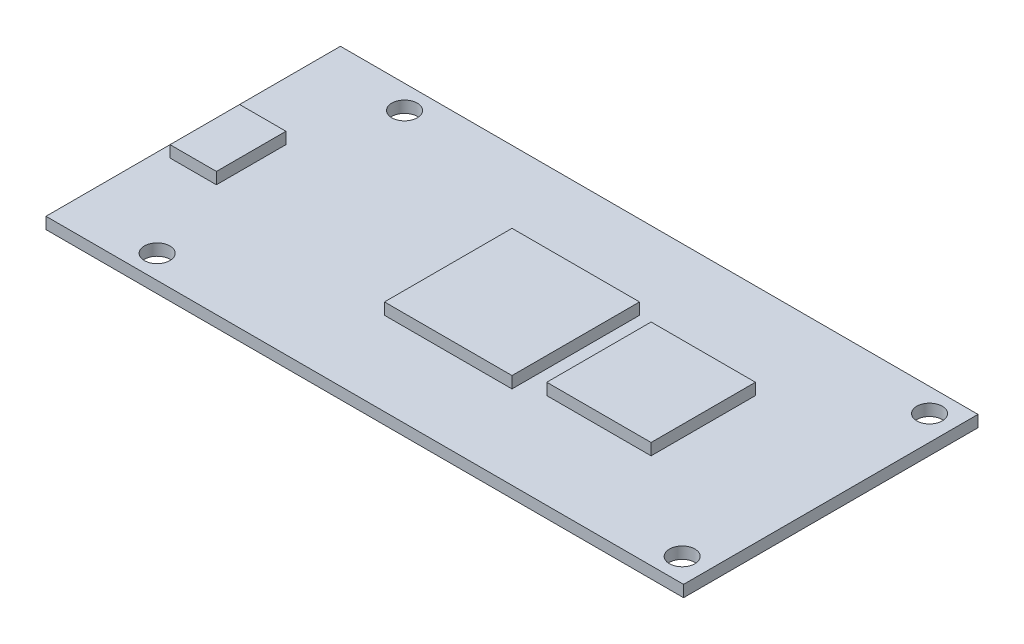
SolidWorks part; units mm, degrees
ref_plane "前视基准面" through (0, 0, 0) normal (0, 0, 1) x (1, 0, 0)
ref_plane "上视基准面" through (0, 0, 0) normal (0, 1, 0) x (1, 0, 0)
ref_plane "右视基准面" through (0, 0, 0) normal (1, 0, 0) x (0, 0, -1)
sketch "草图1" plane through (0, 0, 0) normal (0, 1, 0) x (1, 0, 0)
  line L0 (0, 0) -> (17.7163, 0) construction
  line L1 (-27.5, 12.7) -> (27.5, 12.7)
  line L2 (-27.5, 12.7) -> (-27.5, -12.7)
  line L3 (-27.5, -12.7) -> (27.5, -12.7)
  line L4 (27.5, 12.7) -> (27.5, -12.7)
  line L5 (-27.5, 12.7) -> (27.5, -12.7) construction
  line L6 (-27.5, -12.7) -> (27.5, 12.7) construction
  line L8 (-5.5, 5.5) -> (5.5, 5.5)
  line L9 (-5.5, 5.5) -> (-5.5, -5.5)
  line L10 (-5.5, -5.5) -> (5.5, -5.5)
  line L11 (5.5, 5.5) -> (5.5, -5.5)
  line L12 (-5.5, 5.5) -> (5.5, -5.5) construction
  line L13 (-5.5, -5.5) -> (5.5, 5.5) construction
  line L14 (7.5, 4.5) -> (16.5, 4.5)
  line L15 (7.5, 4.5) -> (7.5, -4.5)
  line L16 (7.5, -4.5) -> (16.5, -4.5)
  line L17 (16.5, 4.5) -> (16.5, -4.5)
  line L18 (7.5, 4.5) -> (16.5, -4.5) construction
  line L19 (7.5, -4.5) -> (16.5, 4.5) construction
  line L20 (-26.5, 3) -> (-22.5, 3)
  line L21 (-26.5, 3) -> (-26.5, -3)
  line L22 (-26.5, -3) -> (-22.5, -3)
  line L23 (-22.5, 3) -> (-22.5, -3)
  line L24 (-26.5, 3) -> (-22.5, -3) construction
  line L25 (-26.5, -3) -> (-22.5, 3) construction
  circle A0 centre (-19.94, 10.67) radius 1.1
  circle A1 centre (25.35, 10.67) radius 1.1
  circle A2 centre (25.35, -10.67) radius 1.1
  circle A3 centre (-19.94, -10.67) radius 1.1
  point P0 (0, 0)
  point P12 (-24.5, 0)
  point P18 (0, 0)
  point P24 (12, 0)
  dimension "D3" = 2.2
  dimension "D4" = 7.56
  dimension "D5" = 45.29
  dimension "D6" = 21.34
  dimension "D1" = 55
  dimension "D2" = 25.4
  dimension "D7" = 11
  dimension "D8" = 9
  dimension "D9" = 2
  dimension "D10" = 6
  dimension "D11" = 4
  dimension "D12" = 1
extrude "凸台-拉伸1" add sketch "草图1" along normal blind 1 contours L20 L23 L22 L2 L3 L4 L1 A2 A1 A0 L8 L11 L10 L9 L14 L17 L16 L15 A3 region at (0, 0, -12.0942)
extrude "凸台-拉伸2" add sketch "草图1<3>" along normal blind 2 contours L23 L20 L2 L22 | L11 L8 L9 L10 | L17 L14 L15 L16 region at (0, 0, 0) region at (12, 0, 0) region at (-24.5, 0, 0)
sketch "草图1<3>" plane through (0, 0, 0) normal (0, 1, 0) x (1, 0, 0) same geometry as "草图1"
